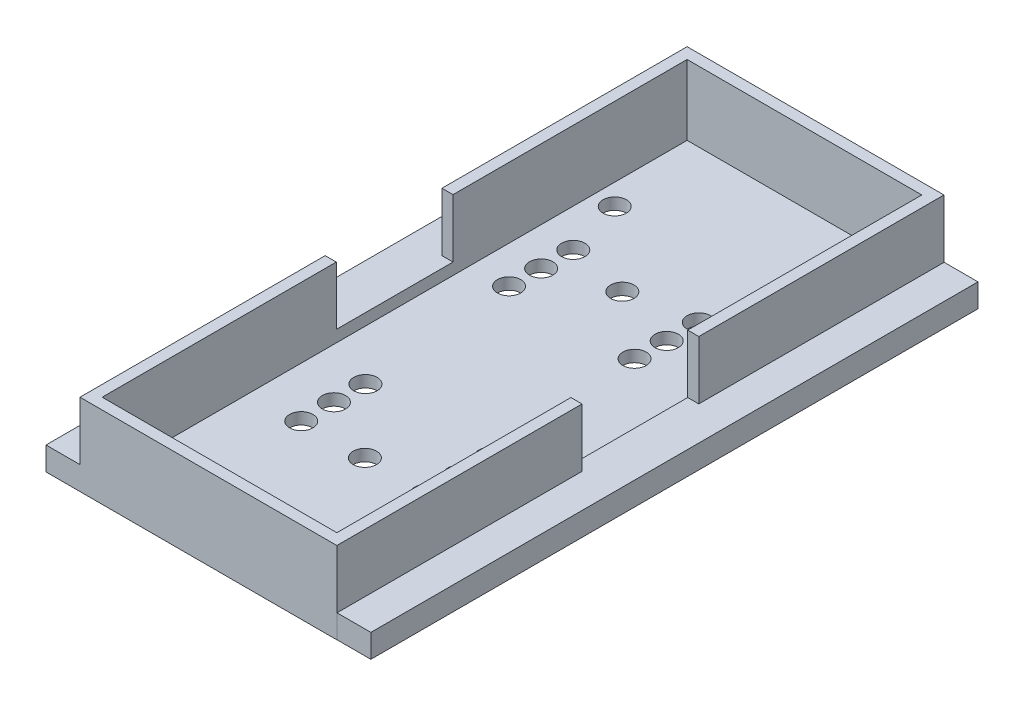
SolidWorks part; units mm, degrees
ref_plane "Front Plane" through (0, 0, 0) normal (0, 0, 1) x (1, 0, 0)
ref_plane "Top Plane" through (0, 0, 0) normal (0, 1, 0) x (1, 0, 0)
ref_plane "Right Plane" through (0, 0, 0) normal (1, 0, 0) x (0, 0, -1)
sketch "Sketch1" plane through (0, 0, 0) normal (0, 1, 0) x (1, 0, 0)
  line L1 (-11, -26) -> (11, -26)
  line L2 (-11, -26) -> (-11, 26)
  line L3 (-11, 26) -> (11, 26)
  line L4 (11, -26) -> (11, 26)
  line L5 (-11, -26) -> (11, 26) construction
  line L6 (-11, 26) -> (11, -26) construction
  point P0 (0, 0)
  dimension "D1" = 52
  dimension "D2" = 22
extrude "Boss-Extrude1" add sketch "Sketch1" along normal blind 7
sketch "Sketch2" plane through (0, 7, 0) normal (0, 1, 0) x (1, 0, 0)
  line L0 (-11, -26) -> (11, -26) construction
  line L1 (-10.05, -25.05) -> (10.05, -25.05)
  line L2 (-10.05, -25.05) -> (-10.05, 25.05)
  line L3 (-10.05, 25.05) -> (10.05, 25.05)
  line L4 (10.05, -25.05) -> (10.05, 25.05)
  line L5 (-10.05, -25.05) -> (10.05, 25.05) construction
  line L6 (-10.05, 25.05) -> (10.05, -25.05) construction
  line L8 (11, -26) -> (11, 26) construction
  point P0 (0, 0)
  dimension "D1" = 0.95
  dimension "D2" = 0.95
extrude "Cut-Extrude1" cut sketch "Sketch2" against normal blind 6
sketch "Sketch3" plane through (0, 0, 0) normal (0, -1, 0) x (1, 0, 0)
  line L0 (0, -25) -> (0, 25) construction
  line L1 (-10, 0) -> (10, 0) construction
  line L2 (11, 26) -> (11, -26) construction
  line L3 (-11, -26) -> (-11, 26) construction
  line L4 (-11, 26) -> (11, 26) construction
  line L5 (11, -26) -> (-11, -26) construction
  line L6 (0, -23) -> (-10, -23) construction
  line L7 (-4.5, -25) -> (-7.5, -24) construction
  point P21 (-6, -24.5)
  dimension "D1" = 1
  dimension "D2" = 1
  dimension "D3" = 1
  dimension "D4" = 1
  dimension "D5" = 2
  dimension "D10" = 6
sketch "Sketch7" plane through (0, 1, 0) normal (0, 1, 0) x (1, 0, 0)
  line L0 (-10.05, 25.05) -> (-10.05, -25.05) construction
  line L3 (-10.05, -25.05) -> (10.05, -25.05) construction
  circle A0 centre (-8.15, -23) radius 0.8
  point P6 (0, 0)
  dimension "D1" = 1.6
  dimension "D2" = 1.9
  dimension "D3" = 2.05
extrude "Cut-Extrude6" cut sketch "Sketch7" against normal through all both and the other way through all
sketch "Sketch8" plane through (0, 1, 0) normal (0, 1, 0) x (1, 0, 0)
  line L0 (-10.05, 25.05) -> (-10.05, -25.05) construction
  line L1 (-10.05, -25.05) -> (10.05, -25.05) construction
  circle A0 centre (-5.75, -12.3) radius 1
  circle A2 centre (5, -12.3) radius 1
  dimension "D1" = 4.3
  dimension "D2" = 12.75
  dimension "D3" = 10.75
extrude "Cut-Extrude7" cut sketch "Sketch8" against normal up to next
sketch "Sketch9" plane through (0, 1, 0) normal (0, 1, 0) x (1, 0, 0)
  line L0 (-10.05, 25.05) -> (-10.05, -25.05) construction
  line L1 (-10.05, -25.05) -> (10.05, -25.05) construction
  circle A0 centre (-5.75, -9.5) radius 1
  circle A1 centre (5, -9.5) radius 1
  dimension "D1" = 4.3
  dimension "D2" = 15.55
  dimension "D3" = 10.75
extrude "Cut-Extrude9" cut sketch "Sketch9" against normal up to next
sketch "Sketch10" plane through (0, 1, 0) normal (0, 1, 0) x (1, 0, 0)
  line L0 (-10.05, 25.05) -> (-10.05, -25.05) construction
  line L1 (-10.05, -25.05) -> (10.05, -25.05) construction
  circle A0 centre (-5.75, -6.8) radius 1
  circle A1 centre (5, -6.8372) radius 1
  dimension "D1" = 4.3
  dimension "D2" = 18.25
  dimension "D3" = 10.75
extrude "Cut-Extrude10" cut sketch "Sketch10" against normal up to next
sketch "Sketch11" plane through (0, 1, 0) normal (0, 1, 0) x (1, 0, 0)
  line L0 (-10.05, -25.05) -> (10.05, -25.05) construction
  line L1 (-10.05, 25.05) -> (-10.05, -25.05) construction
  circle A0 centre (-0.3, -12.3) radius 1
  dimension "D1" = 12.75
  dimension "D2" = 9.75
extrude "Cut-Extrude11" cut sketch "Sketch11" against normal up to next
sketch "Sketch12" plane through (0, 1, 0) normal (0, 1, 0) x (1, 0, 0)
  line L0 (10.05, 25.05) -> (-10.05, 25.05) construction
  line L1 (10.05, -25.05) -> (10.05, 25.05) construction
  circle A0 centre (3.95, 12.05) radius 1
  circle A1 centre (-6.8, 12.05) radius 1
  dimension "D1" = 13
  dimension "D2" = 6.1
  dimension "D3" = 10.75
extrude "Cut-Extrude12" cut sketch "Sketch12" against normal up to next
sketch "Sketch13" plane through (0, 1, 0) normal (0, 1, 0) x (1, 0, 0)
  line L0 (10.05, 25.05) -> (-10.05, 25.05) construction
  line L1 (10.05, -25.05) -> (10.05, 25.05) construction
  circle A0 centre (3.95, 9.3) radius 1
  circle A1 centre (-6.8, 9.3) radius 1
  dimension "D1" = 15.75
  dimension "D2" = 6.1
  dimension "D3" = 10.75
extrude "Cut-Extrude13" cut sketch "Sketch13" against normal up to next
sketch "Sketch14" plane through (0, 1, 0) normal (0, 1, 0) x (1, 0, 0)
  line L0 (10.05, 25.05) -> (-10.05, 25.05) construction
  line L1 (10.05, -25.05) -> (10.05, 25.05) construction
  circle A0 centre (3.9, 6.6) radius 1
  circle A1 centre (-6.85, 6.6) radius 1
  dimension "D1" = 18.45
  dimension "D2" = 6.15
  dimension "D3" = 10.75
extrude "Cut-Extrude14" cut sketch "Sketch14" against normal up to next
sketch "Sketch15" plane through (0, 1, 0) normal (0, 1, 0) x (1, 0, 0)
  line L0 (10.05, 25.05) -> (-10.05, 25.05) construction
  line L1 (-10.05, 25.05) -> (-10.05, -25.05) construction
  circle A0 centre (-1.6, 11.05) radius 1
  dimension "D1" = 14
  dimension "D2" = 8.45
extrude "Cut-Extrude15" cut sketch "Sketch15" against normal up to next
sketch "Sketch16" plane through (0, 1, 0) normal (0, 1, 0) x (1, 0, 0)
  line L0 (10.05, 25.05) -> (-10.05, 25.05) construction
  line L1 (-10.05, 25.05) -> (-10.05, -25.05) construction
  circle A0 centre (-8.25, 17.05) radius 1
  dimension "D1" = 8
  dimension "D2" = 1.8
extrude "Cut-Extrude16" cut sketch "Sketch16" against normal up to next
sketch "Sketch18" plane through (0, 0, 0) normal (0, -1, 0) x (1, 0, 0)
  line L0 (-11, -26) -> (-13.9, -26)
  line L1 (-11, -26) -> (-13.91, -26)
  line L2 (-11, -26) -> (-11, 26)
  line L3 (-11, 26) -> (-13.91, 26)
  line L4 (-13.91, -26) -> (-13.91, 26)
  line L5 (-11, -26) -> (-11, 26)
  line L6 (-11, 26) -> (-13.9, 26)
  line L7 (-13.9, -26) -> (-13.9, 26)
  line L8 (13.9, -26.013) -> (11, -26.013)
  line L9 (13.9, -26.013) -> (13.9, 25.987)
  line L10 (13.9, 25.987) -> (11, 25.987)
  line L11 (11, -26.013) -> (11, 25.987)
  dimension "D1" = 2.91
  dimension "D2" = 52
  dimension "D3" = 22
extrude "Boss-Extrude2" add sketch "Sketch18" against normal blind 2 contours L4 L3 L2 L1
extrude "Boss-Extrude3" add sketch "Sketch18<3>" against normal blind 2 contours L9 L10 L11 L8
sketch "Sketch18<3>" plane through (0, 0, 0) normal (0, -1, 0) x (1, 0, 0) same geometry as "Sketch18"
sketch "Sketch19" plane through (-11, 0, 0) normal (-1, 0, 0) x (0, 0, 1)
  line L0 (-26, 7) -> (26, 7) construction
  line L1 (-5, 7) -> (5, 7)
  line L2 (-5, 7) -> (-5, 2)
  line L3 (-5, 2) -> (5, 2)
  line L4 (5, 7) -> (5, 2)
  line L5 (-26, 2) -> (26, 2) construction
  line L6 (-26, 7) -> (-26, 2) construction
  dimension "D1" = 10
  dimension "D2" = 21
extrude "Cut-Extrude17" cut sketch "Sketch19" against normal through all
